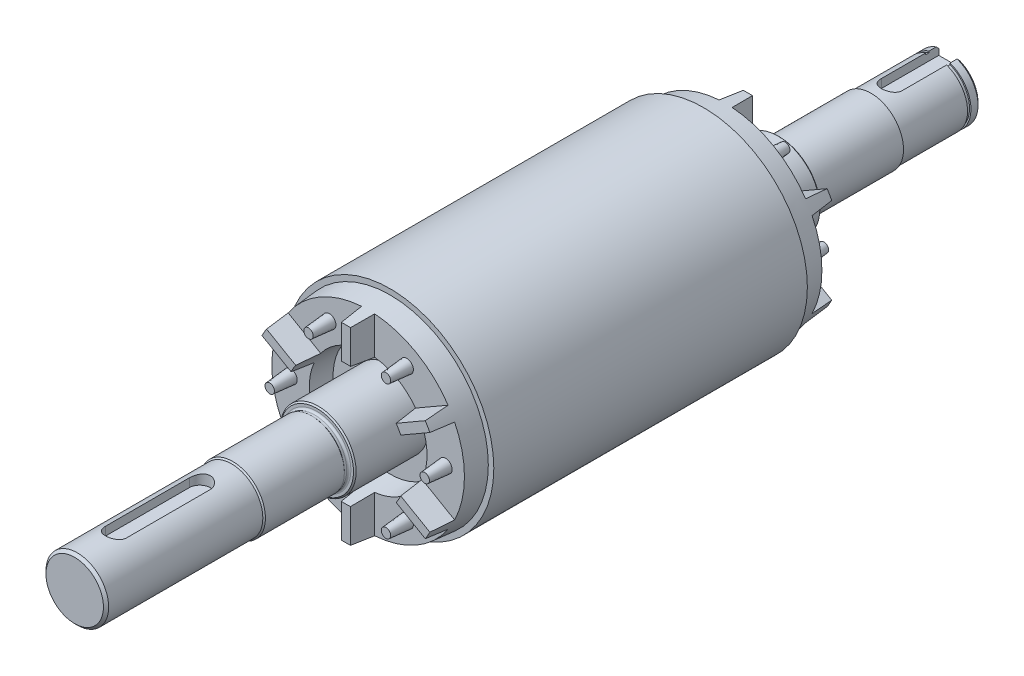
SolidWorks part; units mm, degrees
ref_plane "前视基准面" through (0, 0, 0) normal (0, 0, 1) x (1, 0, 0)
ref_plane "上视基准面" through (0, 0, 0) normal (0, 1, 0) x (1, 0, 0)
ref_plane "右视基准面" through (0, 0, 0) normal (1, 0, 0) x (0, 0, -1)
sketch "草图1" plane through (0, 0, 0) normal (0, 0, 1) x (1, 0, 0)
  circle A0 centre (0, 0) radius 39.7
  dimension "D1" = 79.4
extrude "拉伸1" add sketch "草图1" along normal blind 60
sketch "草图2" plane through (0, 0, 60) normal (0, 0, 1) x (1, 0, 0)
  circle A0 centre (0, 0) radius 37.6
  circle A1 centre (0, 0) radius 21.8
extrude "拉伸2" add sketch "草图2" along normal blind 8.4 draft 5
sketch "草图3" plane through (0, 0, 68.4) normal (0, 0, 1) x (1, 0, 0)
  line L0 (18.1453, 13.363) -> (30.6026, 20.5552)
  line L1 (20.6453, 9.0328) -> (33.1026, 16.2251)
  line L2 (2.5, 22.3958) -> (2.5, 36.7802)
  line L3 (-2.5, 22.3958) -> (-2.5, 36.7802)
  line L4 (20.6453, -9.0328) -> (33.1026, -16.2251)
  line L5 (18.1453, -13.363) -> (30.6026, -20.5552)
  line L6 (2.5, -22.3958) -> (2.5, -36.7802)
  line L7 (-2.5, -22.3958) -> (-2.5, -36.7802)
  line L8 (-18.1453, -13.363) -> (-30.6026, -20.5552)
  line L9 (-20.6453, -9.0328) -> (-33.1026, -16.2251)
  line L10 (-20.6453, 9.0328) -> (-33.1026, 16.2251)
  line L11 (-18.1453, 13.363) -> (-30.6026, 20.5552)
  arc A0 (2.5, 22.3958) -> (-2.5, 22.3958) centre (0, 0) ccw
  arc A1 (2.5, 36.7802) -> (-2.5, 36.7802) centre (0, 0) ccw
  arc A2 (33.1026, 16.2251) -> (30.6026, 20.5552) centre (0, 0) ccw
  arc A3 (20.6453, 9.0328) -> (18.1453, 13.363) centre (0, 0) ccw
  arc A4 (30.6026, -20.5552) -> (33.1026, -16.2251) centre (0, 0) ccw
  arc A5 (18.1453, -13.363) -> (20.6453, -9.0328) centre (0, 0) ccw
  arc A6 (-2.5, -36.7802) -> (2.5, -36.7802) centre (0, 0) ccw
  arc A7 (-2.5, -22.3958) -> (2.5, -22.3958) centre (0, 0) ccw
  arc A8 (-33.1026, -16.2251) -> (-30.6026, -20.5552) centre (0, 0) ccw
  arc A9 (-20.6453, -9.0328) -> (-18.1453, -13.363) centre (0, 0) ccw
  arc A10 (-30.6026, 20.5552) -> (-33.1026, 16.2251) centre (0, 0) ccw
  arc A11 (-18.1453, 13.363) -> (-20.6453, 9.0328) centre (0, 0) ccw
extrude "拉伸3" add sketch "草图3" along normal blind 8.5 draft 5
sketch "草图4" plane through (0, 0, 68.4) normal (0, 0, 1) x (1, 0, 0)
  circle A0 centre (-29.6507, 0) radius 2.5
  circle A1 centre (-14.8253, 25.6782) radius 2.5
  circle A2 centre (14.8253, 25.6782) radius 2.5
  circle A3 centre (29.6507, 0) radius 2.5
  circle A4 centre (14.8253, -25.6782) radius 2.5
  circle A5 centre (-14.8253, -25.6782) radius 2.5
extrude "拉伸4" add sketch "草图4" along normal blind 8 draft 5
mirror "镜向1" about plane through (0, 0, 0) normal (0, 0, 1) of "拉伸4", "拉伸1", "拉伸2", "拉伸3"
sketch "草图6" plane through (0, 0, 60) normal (0, 0, 1) x (1, 0, 0)
  circle A0 centre (0, 0) radius 14.5
extrude "拉伸5" add sketch "草图6" along normal blind 28
sketch "草图7" plane through (0, 0, 88) normal (0, 0, 1) x (1, 0, 0)
  circle A0 centre (0, 0) radius 12.2
extrude "拉伸6" add sketch "草图7" along normal blind 1.7
sketch "草图8" plane through (0, 0, 89.7) normal (0, 0, 1) x (1, 0, 0)
  circle A0 centre (0, 0) radius 12.5
extrude "拉伸7" add sketch "草图8" along normal blind 31
fillet "圆角1" radius 0.8 1 edges at (12.2, 0, 88)
chamfer "倒角1" distance 0.3 angle 45 1 edges at (12.5, 0, 89.7)
chamfer "倒角3" distance 0.5 angle 45 1 edges at (14.5, 0, 88)
sketch "草图9" plane through (0, 0, 120.7) normal (0, 0, 1) x (1, 0, 0)
  circle A0 centre (0, 0) radius 12
extrude "拉伸8" add sketch "草图9" along normal blind 60
chamfer "倒角4" distance 0.5 angle 45 1 edges at (12.5, 0, 120.7)
chamfer "倒角5" distance 1 angle 45 1 edges at (12, 0, 180.7)
ref_plane "基准面1" through (0, 12, 0) normal (0, 1, 0) x (-1, 0, 0)
sketch "草图10" plane through (0, 12, 0) normal (0, 1, 0) x (-1, 0, 0)
  line L2 (4.139, 132.7) -> (4.139, 164.7)
  line L3 (-12, 179.7) -> (12, 179.7) construction
  line L4 (-3.861, 164.7) -> (-3.861, 132.7)
  arc A0 (-3.861, 132.7) -> (4.139, 132.7) centre (0.139, 132.7) ccw
  arc A1 (4.139, 164.7) -> (-3.861, 164.7) centre (0.139, 164.7) ccw
  dimension "D1" = 32
  dimension "D3" = 4
  dimension "D4" = 4
  dimension "D2" = 32
  dimension "D5" = 15
extrude "拉伸9" cut sketch "草图10" against normal blind 4
sketch "草图11" plane through (0, 0, -60) normal (0, 0, -1) x (-1, 0, 0)
  circle A0 centre (0, 0) radius 16
extrude "拉伸10" add sketch "草图11" along normal blind 29
sketch "草图12" plane through (0, 0, -89) normal (0, 0, -1) x (-1, 0, 0)
  circle A0 centre (0, 0) radius 12.2
extrude "拉伸11" add sketch "草图12" along normal blind 1.7
sketch "草图13" plane through (0, 0, -90.7) normal (0, 0, -1) x (-1, 0, 0)
  circle A0 centre (0, 0) radius 12.5
extrude "拉伸12" add sketch "草图13" along normal blind 33.3
fillet "圆角2" radius 0.8 1 edges at (-12.2, 0, -89)
chamfer "倒角6" distance 0.3 angle 45 1 edges at (-12.5, 0, -90.7)
chamfer "倒角7" distance 0.5 angle 45 1 edges at (-16, 0, -89)
sketch "草图14" plane through (0, 0, -124) normal (0, 0, -1) x (-1, 0, 0)
  circle A0 centre (0, 0) radius 12
extrude "拉伸13" add sketch "草图14" along normal blind 25
sketch "草图15" plane through (0, 0, -149) normal (0, 0, -1) x (-1, 0, 0)
  circle A0 centre (0, 0) radius 11.45
extrude "拉伸14" add sketch "草图15" along normal blind 1.3
sketch "草图16" plane through (0, 0, -150.3) normal (0, 0, -1) x (-1, 0, 0)
  circle A0 centre (0, 0) radius 12
extrude "拉伸15" add sketch "草图16" along normal blind 3.7
chamfer "倒角8" distance 1 angle 45 1 edges at (-12, 0, -154)
sketch "草图17" plane through (0, 12, 0) normal (0, 1, 0) x (-1, 0, 0)
  line L1 (-11, -154) -> (11, -154) construction
  line L2 (4, -132) -> (4, -154)
  line L3 (4, -154) -> (-4, -154)
  line L4 (-4, -154) -> (-4, -132)
  arc A0 (4, -132) -> (-4, -132) centre (0, -132) ccw
extrude "拉伸16" cut sketch "草图17" against normal blind 4
scale "缩放比例1" scale about origin uniform scaling yes scale factor 0.25
